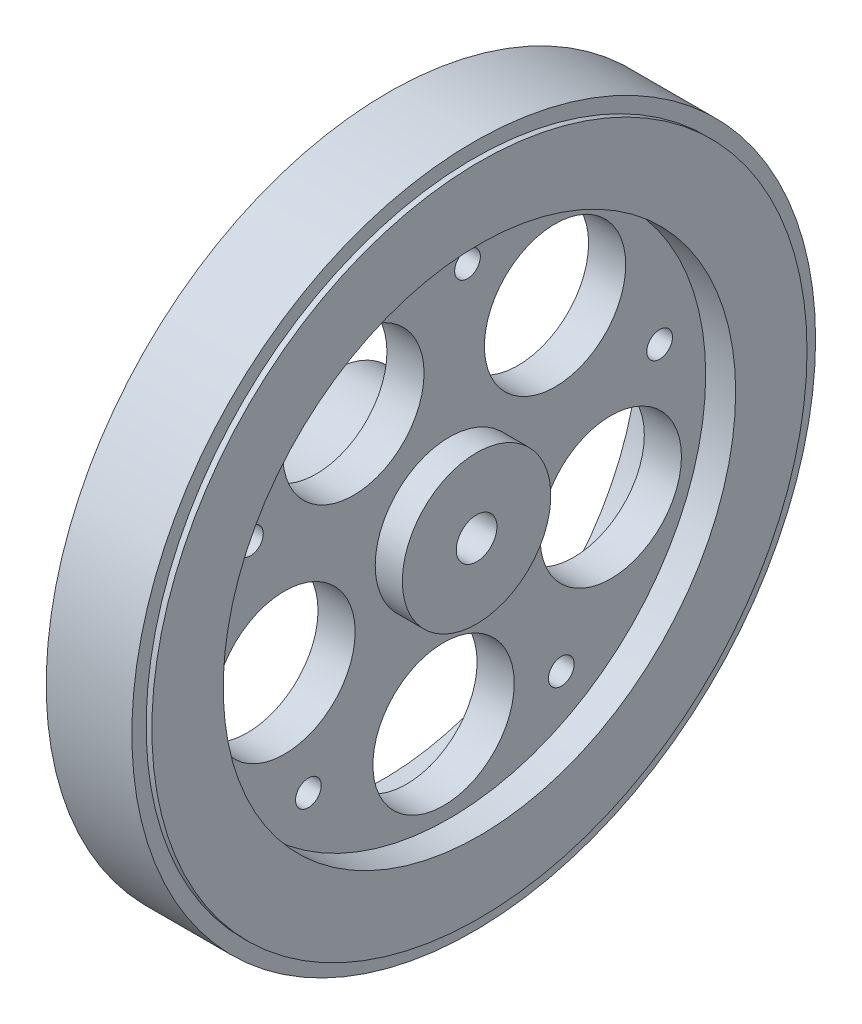
SolidWorks part; units mm, degrees
ref_plane "前视基准面" through (0, 0, 0) normal (0, 0, 1) x (1, 0, 0)
ref_plane "上视基准面" through (0, 0, 0) normal (0, 1, 0) x (1, 0, 0)
ref_plane "右视基准面" through (0, 0, 0) normal (1, 0, 0) x (0, 0, -1)
sketch "草图3" plane through (0, 0, 0) normal (1, 0, 0) x (0, 0, -1)
  circle A0 centre (0, 0) radius 45.9
  dimension "D1" = 91.8
extrude "凸台-拉伸3" add sketch "草图3" along normal mid plane 5.2
sketch "草图4" plane through (0, 0, 0) normal (1, 0, 0) x (0, 0, -1)
  circle A2 centre (0, 0) radius 35.9
  circle A3 centre (0, 0) radius 45.9
  circle A4 centre (0, 0) radius 45.9
  dimension "D1" = 0
  dimension "D2" = 10
extrude "凸台-拉伸4" add sketch "草图4" along normal mid plane 13.6
sketch "草图5" plane through (0, 0, 0) normal (1, 0, 0) x (0, 0, -1)
  circle A3 centre (0, 0) radius 2.85
  point P2 (0, 0)
extrude "切除-拉伸3" cut sketch "草图5" against normal mid plane 13.6 contours A3
sketch "草图13" plane through (-2.6, 0, 0) normal (-1, 0, 0) x (0, 0, 1)
  circle A1 centre (0, 0) radius 10.4
  circle A2 centre (0, 0) radius 2.85
  circle A3 centre (0, 0) radius 2.85
  dimension "D1" = 0
  dimension "D2" = 7.55
extrude "凸台-拉伸5" add sketch "草图13" along normal blind 11
sketch "草图14" plane through (2.6, 0, 0) normal (1, 0, 0) x (0, 0, -1)
  circle A2 centre (0, 0) radius 10.4
  circle A3 centre (0, 0) radius 10.4
  circle A5 centre (0, 0) radius 2.85
  circle A6 centre (0, 0) radius 2.85
  dimension "D1" = 7.55
  dimension "D2" = 0
extrude "凸台-拉伸6" add sketch "草图14" along normal blind 3.8
sketch "草图17" plane through (0, 0, 0) normal (1, 0, 0) x (0, 0, -1)
  circle A0 centre (-13.4598, 19.9308) radius 9.9
  point P0 (-13.4598, 19.9308)
  dimension "D1" = 24.05
extrude "切除-拉伸5" cut sketch "草图17" against normal through all both and the other way through all
ref_axis "基准轴1" through (7.82, 0, 0) along (-1, 0, 0)
pattern_circular "阵列(圆周)1" count 5 over 360 about axis through (7.82, 0, 0) along (-1, 0, 0) of "切除-拉伸5"
sketch "草图19" plane through (0, 0, 0) normal (1, 0, 0) x (0, 0, -1)
  circle A0 centre (-13.4598, 19.9308) radius 9.9 construction
  circle A1 centre (-27.8872, 11.7204) radius 1.8
  point P0 (-27.8872, 11.7204)
  dimension "D1" = 30.25
  dimension "D2" = 16.6
extrude "切除-拉伸6" cut sketch "草图19" against normal through all both and the other way through all
pattern_circular "阵列(圆周)2" count 5 over 360 about axis through (7.82, 0, 0) along (-1, 0, 0) of "切除-拉伸6" reverse direction yes
sketch "草图20" plane through (0, 0, 0) normal (1, 0, 0) x (0, 0, -1)
  circle A2 centre (0, 0) radius 47.9
  circle A3 centre (0, 0) radius 47.9
  circle A6 centre (0, 0) radius 45.9
  circle A7 centre (0, 0) radius 45.9
  dimension "D1" = 2
  dimension "D2" = 0
extrude "凸台-拉伸7" add sketch "草图20" along normal mid plane 12
